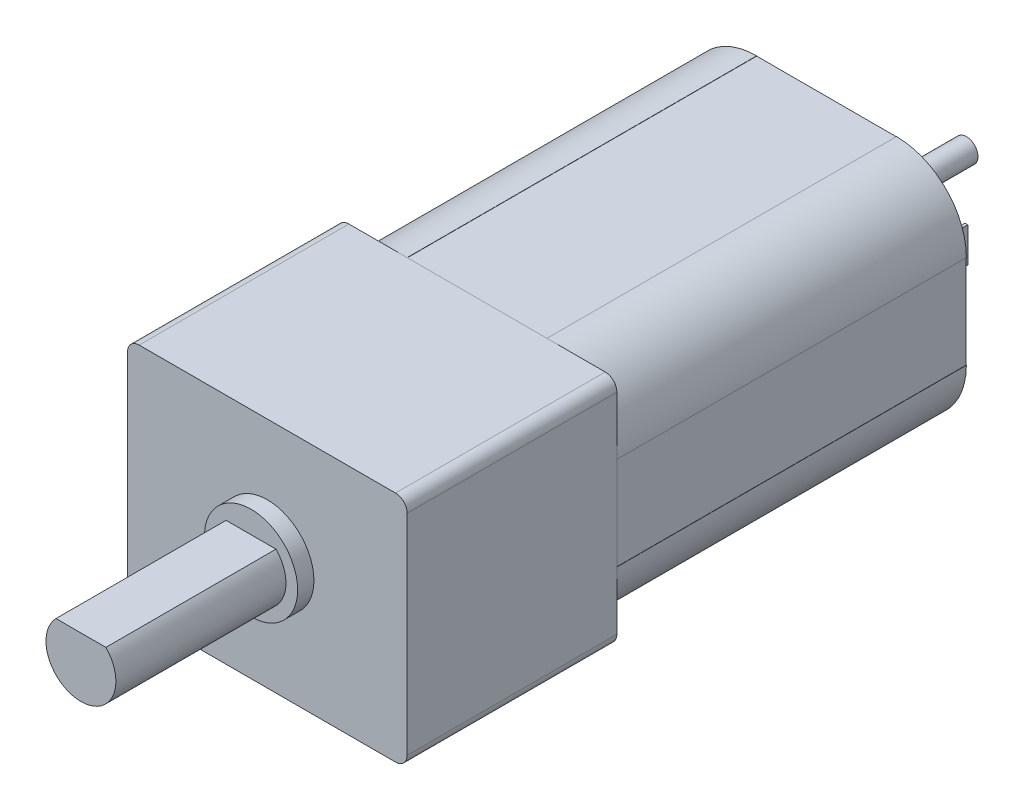
SolidWorks part; units mm, degrees
ref_plane "Ebene vorne" through (0, 0, 0) normal (0, 0, 1) x (1, 0, 0)
ref_plane "Ebene oben" through (0, 0, 0) normal (0, 1, 0) x (1, 0, 0)
ref_plane "Ebene rechts" through (0, 0, 0) normal (1, 0, 0) x (0, 0, -1)
sketch "top" plane through (0, 0, 0) normal (0, 0, 1) x (1, 0, 0)
  line L0 (-6, 5) -> (6, -5) construction
  line L1 (-6, 5) -> (6, 5)
  line L2 (-6, 5) -> (-6, -5)
  line L3 (-6, -5) -> (6, -5)
  line L4 (6, 5) -> (6, -5)
  line L5 (6, 5) -> (-6, -5) construction
  point P4 (0, 0)
  dimension "D1" = 10
  dimension "D2" = 12
extrude "Precision Microdrives Model 212-109" add sketch "top" against normal blind 24
sketch "top ring" plane through (0, 0, 0) normal (0, 0, 1) x (1, 0, 0)
  circle A0 centre (0, 0) radius 2
  dimension "D1" = 4
extrude "top-ring" add sketch "top ring" along normal blind 0.7
hole_wizard "M1-1" positions "Skizze6" profile "Skizze5" hole size "M1" standard "ISO"
sketch "Skizze6" plane through (0, 0, 0) normal (0, 0, 1) x (1, 0, 0)
  line L0 (-6, 0) -> (6, 0) construction
  line L1 (-6, 5) -> (-6, -5) construction
  line L2 (6, -5) -> (6, 5) construction
  point P0 (-4.5, 0)
  dimension "D1" = 4.5
sketch "Skizze5" plane through (-4.5, 0, 0) normal (1, 0, 0) x (0, -1, 0)
  line L0 (0, 0) -> (0, 10.337)
  line L1 (0, 10.337) -> (0.55, 10)
  line L2 (0.55, 10) -> (0.55, 0)
  line L5 (0.55, 0) -> (0, 0)
  line L10 (0, 10.337) -> (-0.55, 10) construction
  line L11 (0, -6.35) -> (0, 107.95) construction
  dimension "Bohrerdurchmesser" = 1.1
  dimension "Bohrungstiefe" = 10
  dimension "Spitzenwinkel" = 117
hole_wizard "M1-2" positions "Skizze8" profile "Skizze7" hole size "M1" standard "ISO"
sketch "Skizze8" plane through (0, 0, 0) normal (0, 0, 1) x (1, 0, 0)
  line L0 (-6, 0) -> (6, 0) construction
  line L1 (-6, 5) -> (-6, -5) construction
  line L2 (6, -5) -> (6, 5) construction
  point P0 (4.5, 0)
  dimension "D1" = 4.5
sketch "Skizze7" plane through (4.5, 0, 0) normal (1, 0, 0) x (0, -1, 0)
  line L0 (0, 0) -> (0, 10.337)
  line L1 (0, 10.337) -> (0.55, 10)
  line L2 (0.55, 10) -> (0.55, 0)
  line L5 (0.55, 0) -> (0, 0)
  line L10 (0, 10.337) -> (-0.55, 10) construction
  line L11 (0, -6.35) -> (0, 107.95) construction
  dimension "Bohrerdurchmesser" = 1.1
  dimension "Bohrungstiefe" = 10
  dimension "Spitzenwinkel" = 117
sketch "Skizze11" plane through (0, 0, 0) normal (0, 0, 1) x (1, 0, 0)
  line L1 (0, 1.05) -> (1.0712, 1.05) construction
  line L2 (0, 1.05) -> (-1.0712, 1.05) construction
  line L3 (-1.0712, 1.05) -> (1.0712, 1.05)
  arc A1 (-1.0712, 1.05) -> (1.0712, 1.05) centre (0, 0) ccw
extrude "D-Shaft" add sketch "Skizze11" along normal blind 8
fillet "Verrundung1" radius 3 4 edges at (-6, 5, -12) (6, 5, -12) (6, -5, -12) (-6, -5, -12)
sketch "Skizze12" plane through (0, 0, -24) normal (0, 0, -1) x (-1, 0, 0)
  circle A0 centre (0, 0) radius 2.5
  dimension "D1" = 5
extrude "bottom" add sketch "Skizze12" along normal blind 1.2
sketch "Skizze13" plane through (0, 0, -24) normal (0, 0, -1) x (-1, 0, 0)
  circle A0 centre (0, 0) radius 0.5
  dimension "D1" = 1
extrude "bolt" add sketch "Skizze13" along normal blind 6
sketch "Skizze14" plane through (0, 0, -24) normal (0, 0, -1) x (-1, 0, 0)
  line L0 (-6, 0) -> (6, 0) construction
  line L1 (-6, -2) -> (-6, 2) construction
  line L2 (6, 2) -> (6, -2) construction
  line L4 (-3.56, 0.75) -> (-3.44, 0.75)
  line L5 (-3.56, 0.75) -> (-3.56, -0.75)
  line L6 (-3.56, -0.75) -> (-3.44, -0.75)
  line L7 (-3.44, 0.75) -> (-3.44, -0.75)
  line L8 (-3.56, 0.75) -> (-3.44, -0.75) construction
  line L9 (-3.56, -0.75) -> (-3.44, 0.75) construction
  line L10 (3.44, 0.75) -> (3.56, 0.75)
  line L11 (3.44, 0.75) -> (3.44, -0.75)
  line L12 (3.44, -0.75) -> (3.56, -0.75)
  line L13 (3.56, 0.75) -> (3.56, -0.75)
  line L14 (3.44, 0.75) -> (3.56, -0.75) construction
  line L15 (3.44, -0.75) -> (3.56, 0.75) construction
  point P6 (-3.5, 0)
  point P11 (3.5, 0)
  dimension "D1" = 1.5
  dimension "D2" = 0.12
  dimension "D3" = 1.5
  dimension "D4" = 0.12
  dimension "D5" = 3.5
  dimension "D6" = 3.5
extrude "flaps" add sketch "Skizze14" along normal blind 2.5
sketch "Skizze15" plane through (-3.56, 0, 0) normal (-1, 0, 0) x (0, 0, 1)
  line L0 (-26.5, -0.75) -> (-26.5, 0.75) construction
  circle A0 centre (-25.7, 0) radius 0.4
  point P2 (-26.5, 0)
  dimension "D1" = 0.8
  dimension "D2" = 0.8
extrude "flap1-cut" cut sketch "Skizze15" against normal up to next
sketch "Skizze16" plane through (3.56, 0, 0) normal (1, 0, 0) x (0, 0, -1)
  line L0 (26.5, 0.75) -> (26.5, -0.75) construction
  circle A0 centre (25.7, 0) radius 0.4
  dimension "D1" = 0.8
  dimension "D2" = 0.8
extrude "flap2-cut" cut sketch "Skizze16" against normal up to next
ref_axis "Achse1" through (0, 0, 8) along (0, 0, -1)
sketch "Skizze21" plane through (0, 5, 0) normal (0, 1, 0) x (1, 0, 0)
  line L0 (6, 24) -> (6, 0) construction
  line L1 (-6, 0) -> (6, 0)
  line L2 (-6, 0) -> (-6, 9)
  line L3 (-6, 9) -> (6, 9)
  line L4 (6, 0) -> (6, 9)
  dimension "D1" = 9
extrude "Aufsatz-Linear austragen2" add sketch "Skizze21" against normal blind 10
sketch "Skizze22" plane through (0, -5, 0) normal (0, -1, 0) x (1, 0, 0)
  line L1 (-3, -9) -> (3, -9)
  line L2 (-3, -9) -> (-3, -24)
  line L3 (-3, -24) -> (3, -24)
  line L4 (3, -9) -> (3, -24)
extrude "Schnitt-Linear austragen3" cut sketch "Skizze22" against normal blind 0.01
sketch "Skizze23" plane through (6, 0, 0) normal (1, 0, 0) x (0, 0, -1)
  line L0 (24, 2) -> (9, 2) construction
  line L1 (9, -2) -> (24, -2)
  line L2 (9, -2) -> (9, 2)
  line L3 (9, 2) -> (24, 2)
  line L4 (24, -2) -> (24, 2)
extrude "Schnitt-Linear austragen4" cut sketch "Skizze23" against normal blind 0.01
sketch "Skizze24" plane through (0, 5, 0) normal (0, 1, 0) x (1, 0, 0)
  line L1 (3, 9) -> (-3, 9)
  line L2 (3, 9) -> (3, 24)
  line L3 (3, 24) -> (-3, 24)
  line L4 (-3, 9) -> (-3, 24)
extrude "Schnitt-Linear austragen5" cut sketch "Skizze24" against normal blind 0.01
sketch "Skizze25" plane through (-6, 0, 0) normal (-1, 0, 0) x (0, 0, 1)
  line L1 (-9, 2) -> (-24, 2)
  line L2 (-9, 2) -> (-9, -2)
  line L3 (-9, -2) -> (-24, -2)
  line L4 (-24, 2) -> (-24, -2)
extrude "Schnitt-Linear austragen6" cut sketch "Skizze25" against normal blind 0.01
fillet "Verrundung2" radius 0.5 4 edges at (-6, -5, -4.5) (6, -5, -4.5) (6, 5, -4.5) (-6, 5, -4.5)
